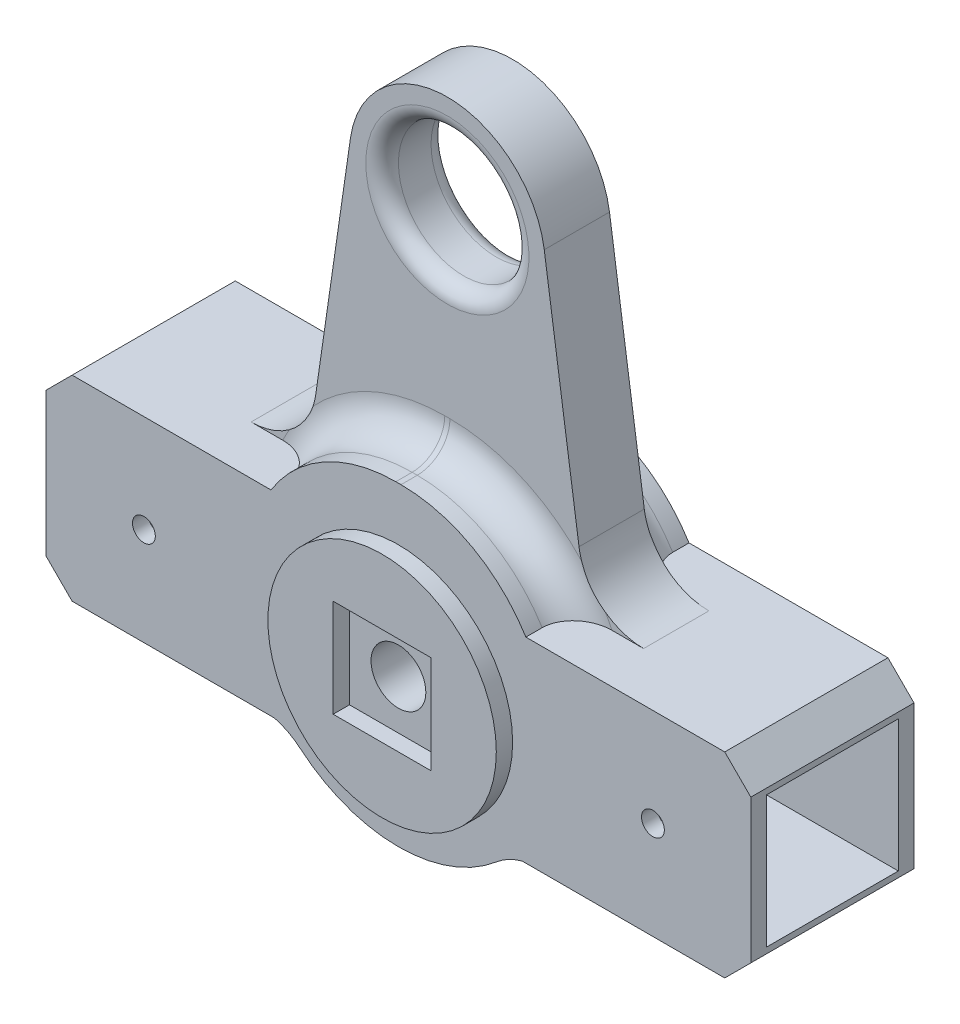
SolidWorks part; units mm, degrees
ref_plane "Alzado" through (0, 0, 0) normal (0, 0, 1) x (1, 0, 0)
ref_plane "Planta" through (0, 0, 0) normal (0, 1, 0) x (1, 0, 0)
ref_plane "Vista lateral" through (0, 0, 0) normal (1, 0, 0) x (0, 0, -1)
sketch "Croquis1" plane through (0, 0, 0) normal (0, 0, 1) x (1, 0, 0)
  line L0 (0, -17.338) -> (0, 18.662) construction
  line L1 (18, 0.662) -> (-18, 0.662) construction
  line L2 (0, 0.662) -> (0, 58.162) construction
  line L3 (-23.0094, 3.9979) -> (-14.8448, 60.3142)
  line L5 (23.0094, 3.9979) -> (14.8448, 60.3142)
  circle A0 centre (0, 0) radius 15
  arc A6 (14.8448, 60.3142) -> (-14.8448, 60.3142) centre (0, 58.162) ccw
  arc A7 (-23.0094, 3.9979) -> (23.0094, 3.9979) centre (0, 0.662) ccw
  circle A8 centre (0, 58.162) radius 10
  point P7 (0, 0.662)
  point P11 (0, 0.662)
  dimension "D1" = 46.5
  dimension "D2" = 30
  dimension "D6" = 30
  dimension "D7" = 20
  dimension "D3" = 18
  dimension "D5" = 57.5
extrude "Saliente-Extruir1" add sketch "Croquis1" along normal mid plane 25
sketch "Croquis3" plane through (0, 0, 0) normal (1, 0, 0) x (0, 0, -1)
  line L1 (12.5, 73.162) -> (-12.5, 73.162) construction
  line L2 (5, 73.162) -> (5, 25.662)
  line L4 (-5, 25.662) -> (-5, 73.162)
  line L6 (-5, 73.162) -> (-12.5, 73.162)
  line L7 (-12.5, 73.162) -> (-12.5, 25.662)
  line L8 (-12.5, 3.9979) -> (-12.5, 60.3142) construction
  line L9 (-12.5, 25.662) -> (-5, 25.662)
  line L10 (5, 25.662) -> (12.5, 25.662)
  line L11 (12.5, 3.9979) -> (12.5, 60.3142) construction
  line L12 (12.5, 25.662) -> (12.5, 73.162)
  line L13 (12.5, 73.162) -> (5, 73.162)
  dimension "D2" = 47.5
  dimension "D3" = 7.5
  dimension "D4" = 7.5
extrude "Cortar-Extruir2" cut sketch "Croquis3" against normal through all both and the other way through all
fillet "Redondeo3" radius 22.5 4 edges at (-19.8686, 25.662, 8.75) (19.8686, 25.662, 8.75) (-19.8686, 25.662, -8.75) (19.8686, 25.662, -8.75)
sketch "Croquis4" plane through (0, 0, -12.5) normal (0, 0, -1) x (-1, 0, 0)
  line L0 (0, 0) -> (-19, 0) construction
  line L1 (-19, 15) -> (-19, -15)
  line L2 (-19, 15) -> (-54, 15)
  line L3 (-54, 15) -> (-54, -15)
  line L4 (-54, -15) -> (-19, -15)
  line L5 (0, 0) -> (0, 9.1483) construction
  line L6 (54, 15) -> (54, -15)
  line L7 (19, 15) -> (54, 15)
  line L8 (19, 15) -> (19, -15)
  line L9 (54, -15) -> (19, -15)
  line L10 (-54, 0) -> (-39, 0) construction
  circle A0 centre (-39, 0) radius 1.75
  circle A1 centre (39, 0) radius 1.75
  point P6 (-19, 0)
  dimension "D4" = 3.5
  dimension "D1" = 30
  dimension "D2" = 19
  dimension "D3" = 35
  dimension "D5" = 15
extrude "Saliente-Extruir2" add sketch "Croquis4" against normal blind 25
sketch "Croquis5" plane through (54, 0, 0) normal (1, 0, 0) x (0, 0, -1)
  line L1 (-10.1, 10.1) -> (10.1, 10.1)
  line L2 (-10.1, 10.1) -> (-10.1, -10.1)
  line L3 (-10.1, -10.1) -> (10.1, -10.1)
  line L4 (10.1, 10.1) -> (10.1, -10.1)
  line L5 (-10.1, 10.1) -> (10.1, -10.1) construction
  line L6 (-10.1, -10.1) -> (10.1, 10.1) construction
  point P0 (0, 0)
  dimension "D1" = 20.2
  dimension "D2" = 20.2
extrude "Cortar-Extruir3" cut sketch "Croquis5" against normal blind 30
mirror "Simetría1" about plane through (0, 0, 0) normal (1, 0, 0) of "Cortar-Extruir3"
fillet "Redondeo4" radius 10 4 edges at (-19, -12.7381, 0) (19, -12.7381, 0) (21.4144, 15, 0) (-21.4144, 15, 0)
chamfer "Chaflán1" distance 4 angle 45 4 edges at (54, 15, 0) (54, -15, 0) (-54, -15, 0) (-54, 15, 0)
fillet "Redondeo5" radius 5 6 edges at (11.3475, 22.8166, -5) (0, 25.662, -5) (-11.3475, 22.8166, 5) (0, 25.662, 5) (-11.3475, 22.8166, -5) (11.3475, 22.8166, 5)
fillet "Redondeo6" radius 2.5 2 edges at (-10, 58.162, 5) (0, 48.162, -5)
sketch "Croquis6" plane through (0, 0, 12.5) normal (0, 0, 1) x (1, 0, 0)
  circle A0 centre (0, 0) radius 11.1
  circle A1 centre (0, 0) radius 17.5
  dimension "D1" = 35
  dimension "D2" = 22.2
extrude "Saliente-Extruir3" add sketch "Croquis6" along normal blind 2.5 and the other way blind 27.5
sketch "Croquis8" plane through (0, 0, 15) normal (0, 0, 1) x (1, 0, 0)
  circle A0 centre (0, 0) radius 17.5
  circle A1 centre (0, 0) radius 4.2
  dimension "D1" = 35
  dimension "D2" = 8.4
extrude "Saliente-Extruir4" add sketch "Croquis8" against normal blind 20
sketch "Croquis9" plane through (0, 0, 15) normal (0, 0, 1) x (1, 0, 0)
  line L1 (-7.5, 7.5) -> (7.5, 7.5)
  line L2 (-7.5, 7.5) -> (-7.5, -7.5)
  line L3 (-7.5, -7.5) -> (7.5, -7.5)
  line L4 (7.5, 7.5) -> (7.5, -7.5)
  line L5 (-7.5, 7.5) -> (7.5, -7.5) construction
  line L6 (-7.5, -7.5) -> (7.5, 7.5) construction
  circle A1 centre (0, 0) radius 4.2
  point P0 (0, 0)
  dimension "D2" = 8.4
  dimension "D1" = 15
extrude "Cortar-Extruir4" cut sketch "Croquis9" against normal blind 2.5 and the other way through all
